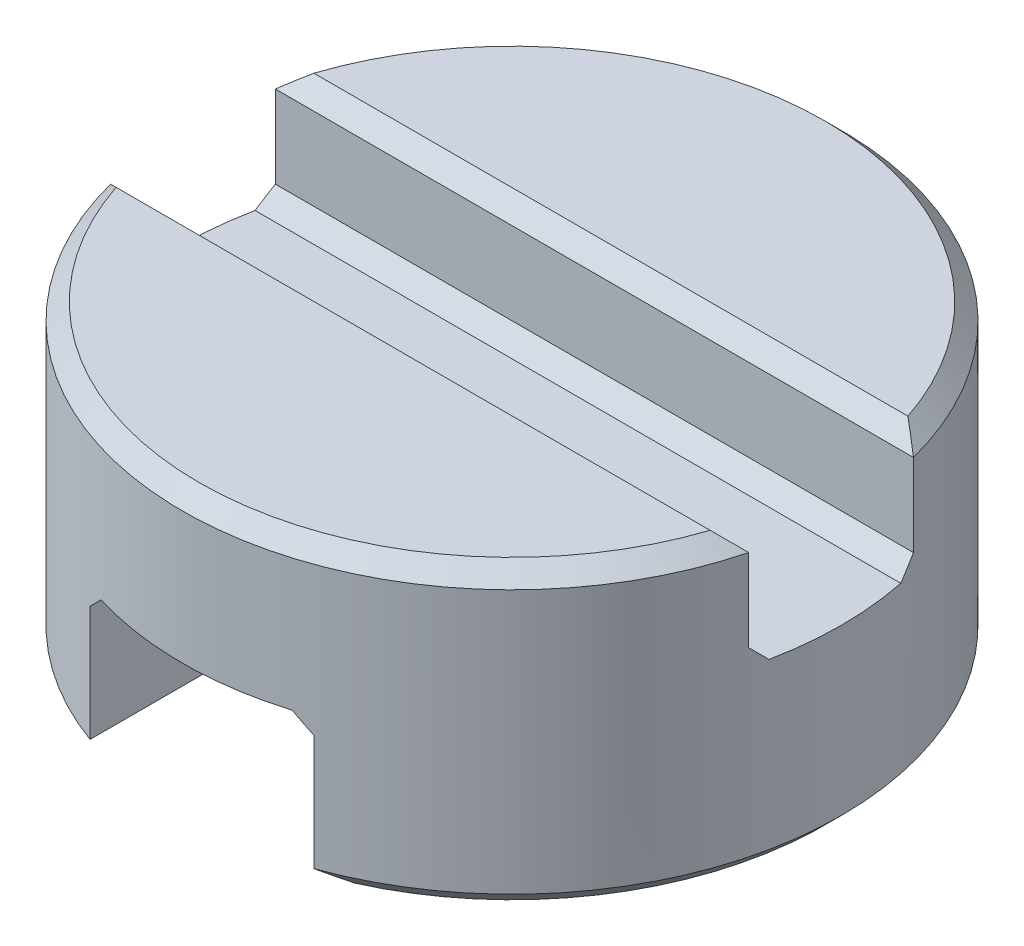
SolidWorks part; units mm, degrees
ref_plane "Спереди" through (0, 0, 0) normal (0, 0, 1) x (1, 0, 0)
ref_plane "Сверху" through (0, 0, 0) normal (0, 1, 0) x (1, 0, 0)
ref_plane "Справа" through (0, 0, 0) normal (1, 0, 0) x (0, 0, -1)
sketch "Эскиз1" plane through (0, 0, 0) normal (0, 1, 0) x (1, 0, 0)
  circle A0 centre (0, 0) radius 10
  dimension "D1" = 20
extrude "Бобышка-Вытянуть1" add sketch "Эскиз1" along normal blind 9
sketch "Эскиз2" plane through (0, 0, 0) normal (0, -1, 0) x (1, 0, 0)
  line L1 (3.4, 10) -> (-3.4, 10)
  line L2 (3.4, 10) -> (3.4, -10)
  line L3 (3.4, -10) -> (-3.4, -10)
  line L4 (-3.4, 10) -> (-3.4, -10)
  line L5 (3.4, 10) -> (-3.4, -10) construction
  line L6 (3.4, -10) -> (-3.4, 10) construction
  circle A0 centre (0, 0) radius 10 construction
  point P0 (0, 0)
  dimension "D1" = 6.8
extrude "Вырез-Вытянуть1" cut sketch "Эскиз2" against normal blind 4.5
chamfer "Фаска1" distance 0.5 angle 45 6 edges at (-10, 0, 0) (-3.4, 0, 0) (10, 0, 0) (3.4, 0, 0) (-3.4, 4.5, 0) (3.4, 4.5, 0)
sketch "Эскиз3" plane through (0, 9, 0) normal (0, 1, 0) x (1, 0, 0)
  line L1 (11, 2.5) -> (-11, 2.5)
  line L2 (11, 2.5) -> (11, -2.5)
  line L3 (11, -2.5) -> (-11, -2.5)
  line L4 (-11, 2.5) -> (-11, -2.5)
  line L5 (11, 2.5) -> (-11, -2.5) construction
  line L6 (11, -2.5) -> (-11, 2.5) construction
  point P0 (0, 0)
  dimension "D1" = 22
  dimension "D2" = 5
extrude "Вырез-Вытянуть2" cut sketch "Эскиз3" against normal blind 3.5
chamfer "Фаска2" distance 0.5 angle 45 6 edges at (0, 9, 10) (0, 9, 2.5) (0, 9, -10) (0, 9, -2.5) (0, 5.5, 2.5) (0, 5.5, -2.5)
equation "\"D1@Бобышка-Вытянуть1\"=5.50мм+3.5"
